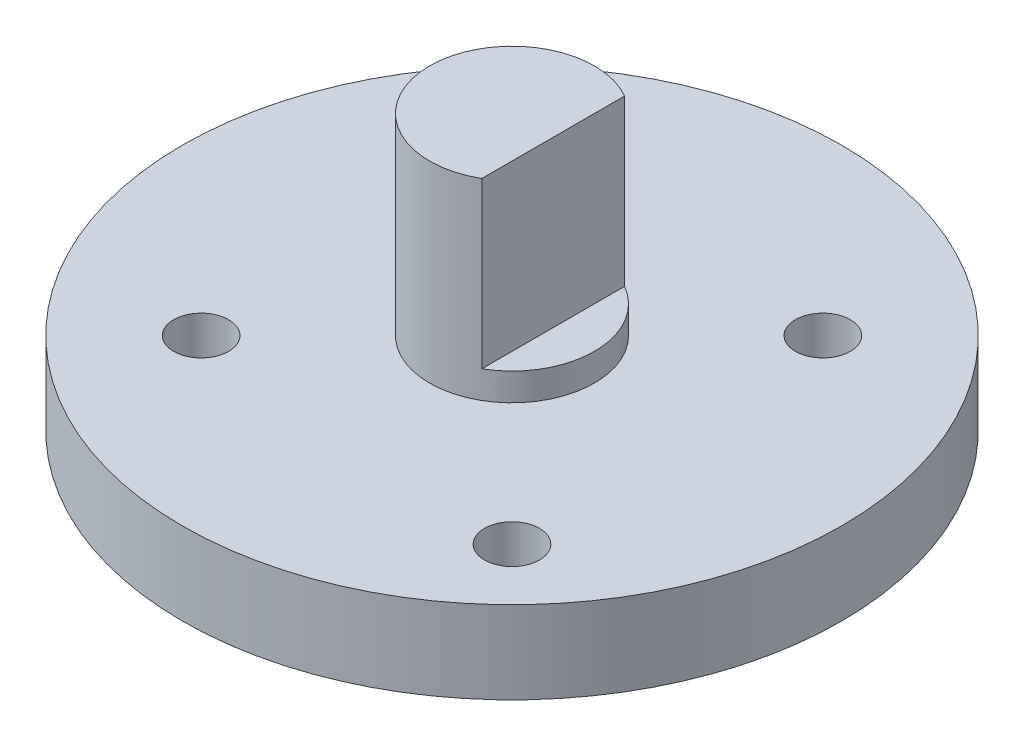
SolidWorks part; units mm, degrees
note: The reader was unsure of these and kept them because the rebuilt part matched: shared geometry of "Croquis1<3>".
ref_plane "Alzado" through (0, 0, 0) normal (0, 0, 1) x (1, 0, 0)
ref_plane "Planta" through (0, 0, 0) normal (0, 1, 0) x (1, 0, 0)
ref_plane "Vista lateral" through (0, 0, 0) normal (1, 0, 0) x (0, 0, -1)
sketch "Croquis1" plane through (0, 0, 0) normal (0, 1, 0) x (1, 0, 0)
  line L0 (0, 0) -> (-6.6149, 6.6149) construction
  line L1 (-6.6149, 6.6149) -> (7.3418, -7.3418) construction
  line L2 (-7.4212, -7.4212) -> (7.838, 7.838) construction
  circle A0 centre (0, 0) radius 12
  circle A1 centre (-6.5761, 6.5761) radius 1
  circle A5 centre (0, 0) radius 3
  circle A8 centre (6.5761, -6.5761) radius 1
  circle A10 centre (0, 0) radius 9.3 construction
  circle A11 centre (6.5761, 6.5761) radius 1 [skipped]
  circle A12 centre (-6.5761, -6.5761) radius 1 [skipped]
  circle A13 centre (0, 0) radius 8 construction
  circle A14 centre (5.6569, 5.6569) radius 1
  circle A15 centre (-5.6569, -5.6569) radius 1
  point P14 (-1.6569, -4)
  point P17 (0, 0)
  point P18 (0, 0)
  point P21 (0, 0)
  point P22 (0, 0)
  point P23 (0, 0)
  dimension "D1" = 24
  dimension "D2" = 2
  dimension "D4" = 18.6
  dimension "D5" = 6
  dimension "D6" = 2
  dimension "D8" = 16
  dimension "D7" = 45
  dimension "D3" = 4
extrude "Saliente-Extruir1" add sketch "Croquis1" along normal blind 3
extrude "Saliente-Extruir2" add sketch "Croquis1<3>" along normal blind 7 from surface at 3
sketch "Croquis1<3>" plane through (0, 0, 0) normal (0, 1, 0) x (1, 0, 0) same geometry as "Croquis1"
sketch "Croquis2" plane through (0, 10, 0) normal (0, 1, 0) x (1, 0, 0)
  line L0 (1.5, 2.5981) -> (1.5, -2.5981)
  circle A0 centre (0, 0) radius 3 construction
  arc A1 (1.5, -2.5981) -> (1.5, 2.5981) centre (0, 0) ccw
  dimension "D1" = 1.5
extrude "Cortar-Extruir1" cut sketch "Croquis2" against normal blind 6
